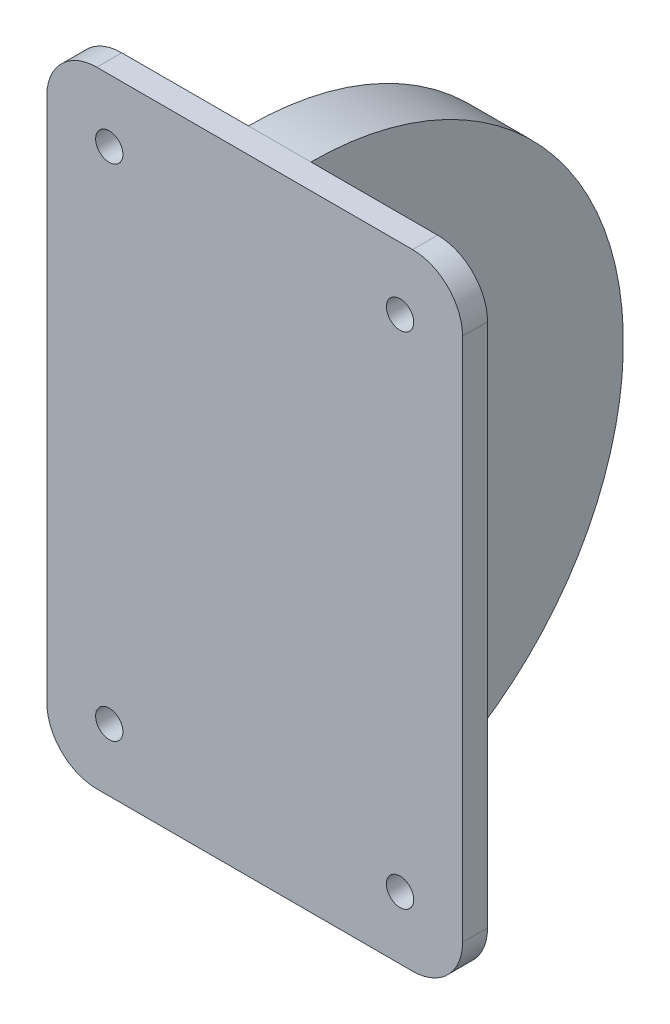
SolidWorks part; units mm, degrees
material "PE High Density"
ref_plane "Front Plane" through (0, 0, 0) normal (0, 0, 1) x (1, 0, 0)
ref_plane "Top Plane" through (0, 0, 0) normal (0, 1, 0) x (1, 0, 0)
ref_plane "Right Plane" through (0, 0, 0) normal (1, 0, 0) x (0, 0, -1)
sketch "Sketch1" plane through (0, 0, 0) normal (0, 0, 1) x (1, 0, 0)
  line L1 (-16.6317, 25) -> (16.6317, 25)
  line L2 (-16.6317, 25) -> (-16.6317, -25)
  line L3 (-16.6317, -25) -> (16.6317, -25)
  line L4 (16.6317, 25) -> (16.6317, -25)
  line L5 (-16.6317, 25) -> (16.6317, -25) construction
  line L6 (-16.6317, -25) -> (16.6317, 25) construction
  point P0 (0, 0)
  dimension "D1" = 50
  dimension "D2" = 33.2634
extrude "Boss-Extrude1" add sketch "Sketch1" along normal blind 2
fillet "Fillet1" radius 4 4 edges at (-16.6317, -25, 1) (16.6317, -25, 1) (-16.6317, 25, 1) (16.6317, 25, 1)
sketch "Sketch2" plane through (0, 0, 2) normal (0, 0, 1) x (1, 0, 0)
  line L0 (12.6317, 25) -> (-12.6317, 25) construction
  line L1 (-16.6317, 21) -> (-16.6317, -21) construction
  line L2 (16.6317, -21) -> (16.6317, 21) construction
  line L3 (-12.6317, -25) -> (12.6317, -25) construction
  circle A0 centre (-11.6317, 20) radius 1.0922
  circle A1 centre (11.6317, 20) radius 1.0922
  circle A2 centre (-11.6317, -20) radius 1.0922
  circle A3 centre (11.6317, -20) radius 1.0922
  dimension "D1" = 2.1844
  dimension "D2" = 2.1844
  dimension "D3" = 2.1844
  dimension "D4" = 2.1844
  dimension "D5" = 5
  dimension "D6" = 5
  dimension "D7" = 5
  dimension "D8" = 5
  dimension "D9" = 5
  dimension "D10" = 5
  dimension "D11" = 5
  dimension "D12" = 5
extrude "Cut-Extrude1" cut sketch "Sketch2" against normal blind 2
cosmetic thread "Cosmetic Thread1" parameters "D2"=3.1844
cosmetic thread "Cosmetic Thread2" parameters "D2"=3.1844
cosmetic thread "Cosmetic Thread3" parameters "D2"=3.1844
cosmetic thread "Cosmetic Thread4" parameters "D2"=3.1844
sketch "Sketch5" plane through (0, 0, 0) normal (1, 0, 0) x (0, 0, -1)
  line L0 (0, 25) -> (0, -25) construction
  line L1 (0, 25) -> (0, -25)
  arc A0 (0, -25) -> (0, 25) centre (0, 0) ccw
  dimension "D1" = 50
extrude "Boss-Extrude2" add sketch "Sketch5" along normal mid plane 5
sketch "Sketch6" plane through (2.5, 0, 0) normal (1, 0, 0) x (0, 0, -1)
  line L0 (0, -21) -> (0, 21) construction
  line L1 (0, -25) -> (-2, -25) construction
  circle A0 centre (10.61, 0) radius 2.5
  dimension "D2" = 5
  dimension "D1" = 10.61
  dimension "D3" = 25
extrude "Cut-Extrude2" cut sketch "Sketch6" against normal blind 5
